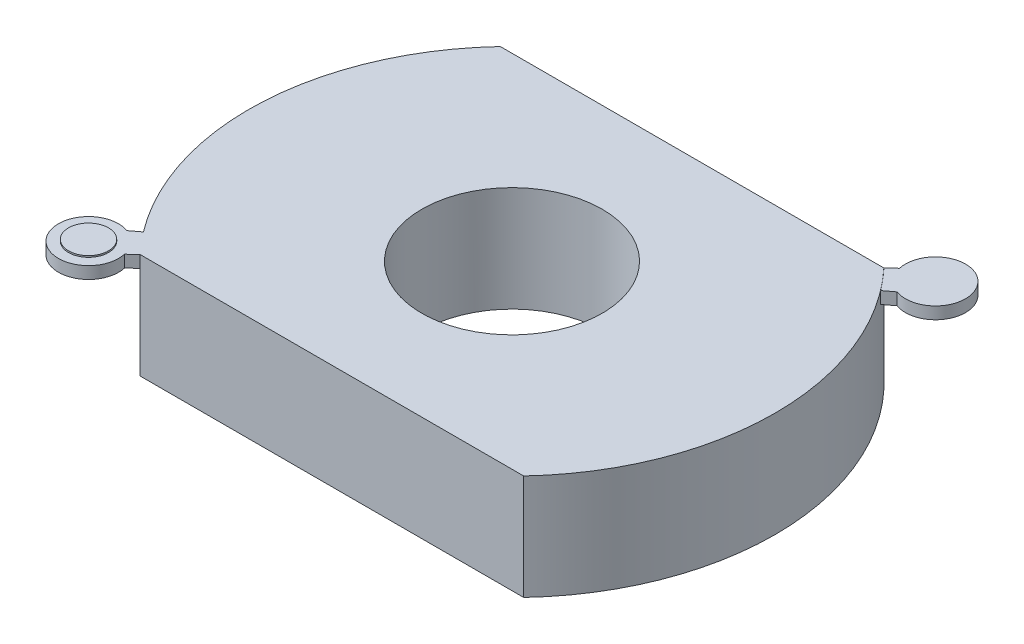
SolidWorks part; units mm, degrees
material "1345 Alloy"
ref_plane "Front Plane" through (0, 0, 0) normal (0, 0, 1) x (1, 0, 0)
ref_plane "Top Plane" through (0, 0, 0) normal (0, 1, 0) x (1, 0, 0)
ref_plane "Right Plane" through (0, 0, 0) normal (1, 0, 0) x (0, 0, -1)
sketch "Sketch1" plane through (0, 0, 0) normal (0, 1, 0) x (1, 0, 0)
  line L0 (-1712.4333, 578.2677) -> (-1658.0172, 559.892) construction
  line L1 (-1682.6566, 611.2885) -> (-1644.8226, 597.5438) construction
  line L2 (-1769.951, 660.0706) -> (-1712.4333, 741.8735) construction
  circle A0 centre (0, 0) radius 1750
  arc A3 (-1712.4333, 578.2677) -> (-1712.4333, 741.8735) centre (-1769.951, 660.0706) cw construction
  arc A4 (-1712.4333, 741.8735) -> (-1682.6566, 611.2885) centre (-1769.951, 660.0706) cw construction
extrude "Boss-Extrude1" add sketch "Sketch1" along normal blind 700
sketch "Sketch9" plane through (0, 0, 0) normal (0, -1, 0) x (1, 0, 0)
  line L1 (-2106.3119, -1198.0599) -> (2106.3119, -1198.0599)
  line L2 (-2106.3119, -1198.0599) -> (-2106.3119, 1198.0599)
  line L3 (-2106.3119, 1198.0599) -> (2106.3119, 1198.0599)
  line L4 (2106.3119, -1198.0599) -> (2106.3119, 1198.0599)
  line L5 (-2106.3119, -1198.0599) -> (2106.3119, 1198.0599) construction
  line L6 (-2106.3119, 1198.0599) -> (2106.3119, -1198.0599) construction
  line L7 (-2636.6179, -2082.9122) -> (2636.6179, -2082.9122)
  line L8 (-2636.6179, -2082.9122) -> (-2636.6179, 2082.9122)
  line L9 (-2636.6179, 2082.9122) -> (2636.6179, 2082.9122)
  line L10 (2636.6179, -2082.9122) -> (2636.6179, 2082.9122)
  line L11 (-2636.6179, -2082.9122) -> (2636.6179, 2082.9122) construction
  line L12 (-2636.6179, 2082.9122) -> (2636.6179, -2082.9122) construction
  point P0 (0, 0)
  point P6 (0, 0)
extrude "Cut-Extrude10" cut sketch "Sketch9" against normal through all both and the other way through all
sketch "Sketch3" plane through (0, 0, 0) normal (0, -1, 0) x (1, 0, 0)
  circle A0 centre (0, 0) radius 600
extrude "Cut-Extrude3" cut sketch "Sketch3" against normal through all both and the other way through all
shell "Shell1" thickness 1.5 removed face at (0, 0, 600)
sketch "Sketch12" plane through (0, 700, 0) normal (0, 1, 0) x (1, 0, 0)
  line L0 (-1275.7204, -1197.9305) -> (-1329.4274, -1248.3625)
  line L1 (-1275.7204, -1197.9305) -> (-1329.4274, -1248.3625)
  line L2 (-1456.8867, -1104.0663) -> (-1394.7434, -1056.9725)
  line L3 (-1212.6439, -1163.1539) -> (-1394.7434, -1056.9725) construction
  line L4 (-1329.4274, -1248.3625) -> (-1275.8583, -1198.0599) construction
  line L5 (1275.5989, -1198.0599) -> (-1275.5989, -1198.0599) construction
  line L6 (-1275.5989, 1198.0599) -> (1275.5989, -1198.0599) construction
  line L7 (0, 0) -> (-1750, 0) construction
  line L13 (0, 0) -> (0, 1750) construction
  line L14 (1212.6439, 1163.1539) -> (1394.7434, 1056.9725) construction
  line L15 (1329.4274, 1248.3625) -> (1275.8583, 1198.0599) construction
  line L16 (1275.7204, 1197.9305) -> (1329.4274, 1248.3625)
  line L17 (1275.7204, 1197.9305) -> (1329.4274, 1248.3625)
  line L18 (1456.8867, 1104.0663) -> (1394.7434, 1056.9725)
  arc A0 (-1275.5989, -1198.0599) -> (-1524.5473, -859.2179) centre (0, 0) cw
  arc A1 (-1275.7204, 1197.9305) -> (-1275.5989, 1198.0599) centre (0, 0) ccw construction
  arc A2 (-1329.4274, -1248.3625) -> (-1456.8867, -1104.0663) centre (-1524.5473, -1292.2737) cw
  arc A3 (-1275.7204, -1197.9305) -> (-1275.5989, -1198.0599) centre (0, 0) cw construction
  arc A4 (1275.8583, 1198.0599) -> (1394.7434, 1056.9725) centre (24.3381, 22.854) cw
  arc A6 (1329.4274, 1248.3625) -> (1456.8867, 1104.0663) centre (1524.5473, 1292.2737) cw
  arc M6 (-1275.5989, 1198.0599) -> (-1275.5989, -1198.0599) centre (0, 0) ccw
extrude "Boss-Extrude2" add sketch "Sketch12" against normal blind 80 contours A2 L0 L2 M6 region at (-1511.5348, 700, 1280.7775)
extrude "Boss-Extrude3" add sketch "Sketch12<6>" against normal blind 80 separate body contours A6 L17 A4 L18 region at (1511.5672, 700, -1280.8004)
sketch "Sketch12<6>" plane through (0, 700, 0) normal (0, 1, 0) x (1, 0, 0) same geometry as "Sketch12"
sketch "Sketch13" plane through (0, 698.5, 0) normal (0, -1, 0) x (-1, 0, 0)
  line L0 (938.2248, -598.28) -> (838.2248, -598.28) construction
  line L1 (938.2248, -598.28) -> (1274.9496, -1196.5599)
  line L2 (838.2248, -598.28) -> (838.2248, -698.28) construction
  line L3 (838.2248, -698.28) -> (1038.2248, -698.28) construction
  line L4 (1038.2248, -698.28) -> (1038.2248, -498.28) construction
  line L5 (938.2248, -598.28) -> (1274.9496, -1196.5599) construction
  line L6 (1274.9496, 1196.5599) -> (938.2248, -598.28) construction
  line L7 (1274.9496, -1196.5599) -> (1274.9496, 1196.5599) construction
  line L8 (1038.2248, -498.28) -> (838.2248, -498.28) construction
  line L9 (838.2248, -498.28) -> (838.2248, -598.28) construction
  line L10 (838.2248, -498.28) -> (838.2248, -698.28)
  line L11 (838.2248, -698.28) -> (1038.2248, -698.28)
  line L12 (1038.2248, -698.28) -> (1038.2248, -498.28)
  line L13 (1038.2248, -498.28) -> (838.2248, -498.28)
  circle A1 centre (938.2248, -598.28) radius 27.5
extrude "Boss-Extrude4" add sketch "Sketch13" along normal blind 50 contours A1 L11 L12 L13 L10 region at (-916.3659, 698.5, 695.4515)
sketch "Sketch14" plane through (0, 700, 0) normal (0, 1, 0) x (1, 0, 0)
  circle A0 centre (-1524.5473, -1292.2737) radius 132.8125
extrude "Boss-Extrude5" add sketch "Sketch14" along normal blind 10
